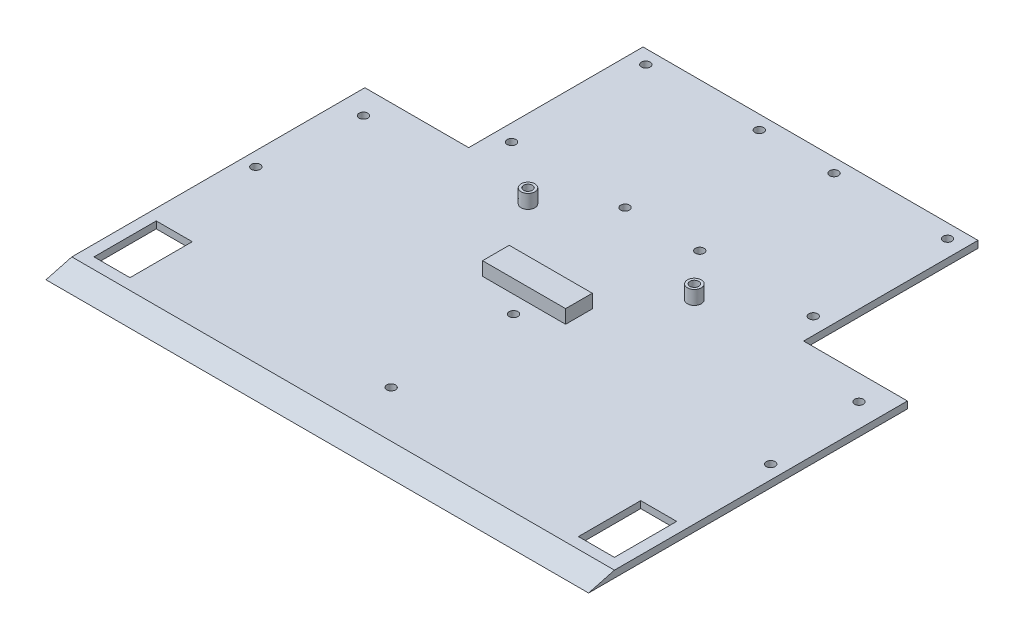
SolidWorks part; units mm, degrees
ref_plane "Alzado" through (0, 0, 0) normal (0, 0, 1) x (1, 0, 0)
ref_plane "Planta" through (0, 0, 0) normal (0, 1, 0) x (1, 0, 0)
ref_plane "Vista lateral" through (0, 0, 0) normal (1, 0, 0) x (0, 0, -1)
sketch "Croquis1" plane through (0, 0, 0) normal (1, 0, 0) x (0, 0, -1)
  line L0 (0, 0) -> (178.17, 0)
  line L1 (178.17, 0) -> (178.17, 2.5)
  line L2 (178.17, 2.5) -> (9.3301, 2.5)
  line L3 (0, 0) -> (9.3301, 2.5)
  dimension "D1" = 178.17
  dimension "D2" = 2.5
  dimension "D3" = 165
extrude "Saliente-Extruir1" add sketch "Croquis1" along normal blind 196
sketch "Croquis2" plane through (0, 0, 0) normal (0, -1, 0) x (-1, 0, 0)
  line L1 (-37.5, 115.1801) -> (0, 115.1801)
  line L2 (-37.5, 115.1801) -> (-37.5, 178.17)
  line L3 (-37.5, 178.17) -> (0, 178.17)
  line L4 (0, 115.1801) -> (0, 178.17)
  line L5 (-37.5, 115.1801) -> (0, 178.17) construction
  line L6 (-37.5, 178.17) -> (0, 115.1801) construction
  line L7 (-158.5, 115.1801) -> (-196, 115.1801)
  line L8 (-158.5, 115.1801) -> (-158.5, 178.17)
  line L9 (-158.5, 178.17) -> (-196, 178.17)
  line L10 (-196, 115.1801) -> (-196, 178.17)
  line L11 (-158.5, 115.1801) -> (-196, 178.17) construction
  line L12 (-158.5, 178.17) -> (-196, 115.1801) construction
  point P4 (-18.75, 146.6751)
  point P11 (-177.25, 146.6751)
extrude "Cortar-Extruir1" cut sketch "Croquis2" against normal up to next
sketch "Croquis4" plane through (0, 2.5, 0) normal (0, 1, 0) x (1, 0, 0)
  line L7 (4, 13.3301) -> (17, 13.3301)
  line L8 (4, 13.3301) -> (4, 35.8301)
  line L9 (4, 35.8301) -> (17, 35.8301)
  line L10 (17, 13.3301) -> (17, 35.8301)
  line L11 (4, 13.3301) -> (17, 35.8301) construction
  line L12 (4, 35.8301) -> (17, 13.3301) construction
  point P9 (10.5, 24.5801)
  dimension "D3" = 22.5
  dimension "D4" = 13
extrude "Cortar-Extruir2" cut sketch "Croquis4" against normal up to next
ref_plane "Plano1" through (98, 0, 0) normal (1, 0, 0) x (0, 0, -1)
mirror "Simetría1" about plane through (98, 0, 0) normal (1, 0, 0) of "Cortar-Extruir2"
sketch "Sketch1" plane through (0, 2.5, 0) normal (0, 1, 0) x (1, 0, 0)
  circle A0 centre (187.5, 106.1801) radius 1.585
  circle A1 centre (8.5, 106.1801) radius 1.585
extrude "Cut-Extrude1" cut sketch "Sketch1" against normal up to next
sketch "Sketch2" plane through (0, 2.5, 0) normal (0, 1, 0) x (1, 0, 0)
  circle A0 centre (98.5, 26.1801) radius 1.585
extrude "Cut-Extrude2" cut sketch "Sketch2" against normal up to next
sketch "Sketch3" plane through (0, 2.5, 0) normal (0, 1, 0) x (1, 0, 0)
  circle A0 centre (111.5, 124.67) radius 1.585
  circle A1 centre (152.5, 124.67) radius 1.585
  circle A2 centre (152.5, 173.17) radius 1.585
  circle A3 centre (111.5, 173.17) radius 1.585
  circle A4 centre (84.5, 173.17) radius 1.585
  circle A5 centre (43.5, 173.17) radius 1.585
  circle A6 centre (43.5, 124.67) radius 1.585
  circle A7 centre (84.5, 124.67) radius 1.585
extrude "Cut-Extrude3" cut sketch "Sketch3" against normal up to next
sketch "Sketch4" plane through (0, 2.5, 0) normal (0, 1, 0) x (1, 0, 0)
  circle A0 centre (125.8764, 108.3369) radius 1.6
  circle A1 centre (65.7764, 108.3369) radius 1.6
  circle A2 centre (65.7764, 108.3369) radius 2.5
  circle A3 centre (125.8764, 108.3369) radius 2.5
  dimension "D1" = 5
  dimension "D2" = 5
extrude "Boss-Extrude1" add sketch "Sketch4" along normal blind 5
sketch "Sketch5" plane through (0, 2.5, 0) normal (0, 1, 0) x (1, 0, 0)
  line L1 (80.272, 87.0616) -> (110.272, 87.0616)
  line L2 (80.272, 87.0616) -> (80.272, 77.4239)
  line L3 (80.272, 77.4239) -> (110.272, 77.4239)
  line L4 (110.272, 87.0616) -> (110.272, 77.4239)
  line L5 (80.272, 87.0616) -> (110.272, 77.4239) construction
  line L6 (80.272, 77.4239) -> (110.272, 87.0616) construction
  point P4 (96.9958, 82.487)
extrude "Boss-Extrude2" add sketch "Sketch5" along normal blind 4.9
sketch "Sketch6" plane through (0, 2.5, 0) normal (0, 1, 0) x (1, 0, 0)
  circle A0 centre (125.8764, 108.3369) radius 1.6
  circle A1 centre (65.7764, 108.3369) radius 1.6
extrude "Cut-Extrude4" cut sketch "Sketch6" against normal blind 4.9
sketch "Sketch7" plane through (0, 2.5, 0) normal (0, 1, 0) x (1, 0, 0)
  circle A0 centre (5.0671, 70.7278) radius 1.585
  circle A1 centre (97.6819, 71.2085) radius 1.585
  circle A2 centre (191.0671, 70.7278) radius 1.585
extrude "Cut-Extrude5" cut sketch "Sketch7" against normal blind 10
